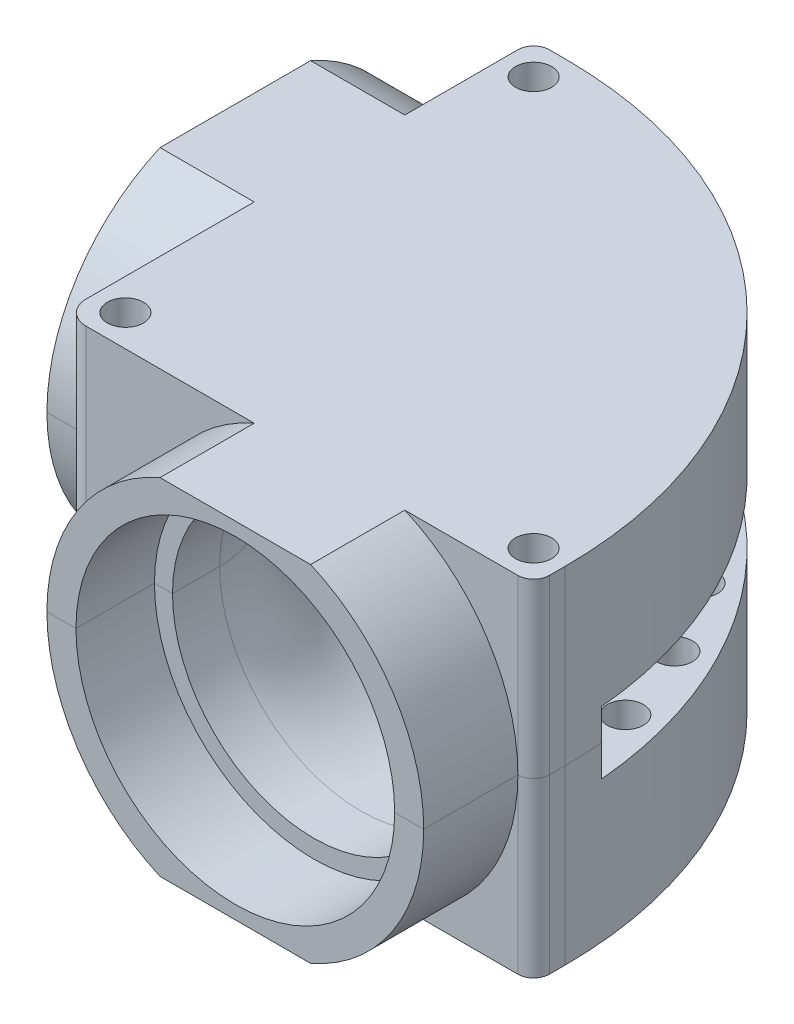
SolidWorks part; units mm, degrees
material "ABS"
ref_plane "前视基准面" through (0, 0, 0) normal (0, 0, 1) x (1, 0, 0)
ref_plane "上视基准面" through (0, 0, 0) normal (0, 1, 0) x (1, 0, 0)
ref_plane "右视基准面" through (0, 0, 0) normal (1, 0, 0) x (0, 0, -1)
sketch "草图1" plane through (0, 0, 0) normal (0, 1, 0) x (1, 0, 0)
  line L0 (2, 0) -> (28, 0)
  line L1 (0, 2) -> (0, 28)
  arc A0 (28, 0) -> (0, 28) centre (0, 0) ccw
  arc A1 (2, 0) -> (0, 2) centre (0, 0) ccw
  dimension "D1" = 56
  dimension "D2" = 4
extrude "凸台-拉伸1" add sketch "草图1" along normal mid plane 22
sketch "草图9" plane through (0, 0, 0) normal (0, 1, 0) x (1, 0, 0)
  circle A0 centre (0, 0) radius 15
  dimension "D1" = 30
sweep "切除-扫描2" cut path "草图9" circular profile diameter 18 parameters "D3"=18
sketch "草图16" plane through (0, 0, 0) normal (0, 0, 1) x (1, 0, 0)
  line L1 (2, 11) -> (28, 11)
  line L2 (2, 11) -> (2, -11)
  line L3 (2, -11) -> (28, -11)
  line L4 (28, 11) -> (28, -11)
  circle A0 centre (15, 0) radius 9
extrude "凸台-拉伸3" add sketch "草图16" along normal blind 2
sketch "草图17" plane through (0, 0, 0) normal (-1, 0, 0) x (0, 0, 1)
  line L1 (-28, 11) -> (-2, 11)
  line L2 (-28, 11) -> (-28, -11)
  line L3 (-28, -11) -> (-2, -11)
  line L4 (-2, 11) -> (-2, -11)
  circle A0 centre (-15, 0) radius 9
extrude "凸台-拉伸4" add sketch "草图17" along normal blind 2
sketch "草图18" plane through (0, 0, 2) normal (0, 0, 1) x (1, 0, 0)
  line L0 (10.2042, 11) -> (19.7958, 11)
  line L1 (28, 11) -> (2, 11) construction
  line L2 (10.2042, -11) -> (19.7958, -11)
  line L3 (2, -11) -> (28, -11) construction
  circle A0 centre (15, 0) radius 9
  arc A1 (19.7958, -11) -> (19.7958, 11) centre (15, 0) ccw
  arc A2 (10.2042, 11) -> (10.2042, -11) centre (15, 0) ccw
  dimension "D1" = 24
  dimension "D2" = 18
extrude "凸台-拉伸5" add sketch "草图18" along normal blind 6
sketch "草图19" plane through (-2, 0, 0) normal (-1, 0, 0) x (0, 0, 1)
  line L0 (-19.7958, 11) -> (-10.2042, 11)
  line L1 (-2, 11) -> (-28, 11) construction
  line L2 (-19.7958, -11) -> (-10.2042, -11)
  line L3 (-28, -11) -> (-2, -11) construction
  circle A0 centre (-15, 0) radius 9
  arc A1 (-19.7958, 11) -> (-19.7958, -11) centre (-15, 0) ccw
  arc A2 (-10.2042, -11) -> (-10.2042, 11) centre (-15, 0) ccw
  dimension "D1" = 18
  dimension "D2" = 24
extrude "凸台-拉伸6" add sketch "草图19" along normal blind 6
sketch "草图21" plane through (0, 0, 0) normal (0, 1, 0) x (1, 0, 0)
  line L0 (-2, 2) -> (-2, -2)
  line L1 (-2, -2) -> (2, -2)
  line L2 (-2, 2) -> (0, 2)
  line L3 (2, -2) -> (2, 0)
  arc A0 (0, 2) -> (2, 0) centre (0, 0) cw
extrude "凸台-拉伸8" add sketch "草图21" along normal blind 11 and the other way blind 11
sketch "草图23" plane through (0, 0, 0) normal (0, 1, 0) x (1, 0, 0)
  circle A0 centre (0, 0) radius 1.15
  dimension "D1" = 2.3
extrude "切除-拉伸1" cut sketch "草图23" against normal blind 13 and the other way blind 14
sketch "草图24" plane through (0, 0, 0) normal (0, 1, 0) x (1, 0, 0)
  line L1 (0, 0) -> (0, 40.7422) construction
  circle A0 centre (26, 0) radius 1.15
  circle A2 centre (0, 0) radius 1.15 construction
  dimension "D1" = 26
  dimension "D2" = 2.3
extrude "切除-拉伸2" cut sketch "草图24" against normal blind 11 and the other way blind 11
sketch "草图25" plane through (0, 0, 0) normal (0, 1, 0) x (1, 0, 0)
  line L0 (0, 31.2597) -> (0, -3.7756) construction
  circle A0 centre (0, 26) radius 1.15
  circle A1 centre (0, 0) radius 1.15 construction
  dimension "D1" = 2.3
  dimension "D2" = 26
extrude "切除-拉伸3" cut sketch "草图25" against normal blind 11 and the other way blind 11
sketch "草图26" plane through (0, 0, 0) normal (0, 1, 0) x (1, 0, 0)
  line L0 (0, 0) -> (0, 30.8638) construction
  line L1 (0, 0) -> (32.3971, 0) construction
  line L2 (0, 0) -> (25.3664, 25.3664) construction
  line L3 (0, 0) -> (28.117, 22.7687) construction
  line L4 (0, 0) -> (33.1084, 16.8695) construction
  line L5 (0, 0) -> (38.2313, 10.2441) construction
  line L6 (19.9239, 1.7431) -> (29.8858, 2.6147)
  line L7 (1.7431, 19.9239) -> (2.6147, 29.8858)
  arc A0 (29.8858, 2.6147) -> (2.6147, 29.8858) centre (0, 0) ccw
  arc A1 (19.9239, 1.7431) -> (1.7431, 19.9239) centre (0, 0) ccw
  circle A2 centre (0, 0) radius 26 construction
  circle A3 centre (25.1141, 6.7293) radius 1.15 construction
  dimension "D1" = 60
  dimension "D2" = 40
  dimension "D7" = 52
  dimension "D8" = 2.3
  dimension "D3" = 45
  dimension "D4" = 6
  dimension "D5" = 12
  dimension "D6" = 12
  dimension "D9" = 40
extrude "切除-拉伸6" cut sketch "草图26" against normal blind 2 and the other way blind 2
sketch "草图27" plane through (0, 0, 0) normal (0, 1, 0) x (1, 0, 0)
  line L0 (0, 0) -> (38.2313, 10.2441) construction
  line L1 (0, 0) -> (33.1084, 16.8695) construction
  line L2 (0, 0) -> (28.117, 22.7687) construction
  line L3 (0, 0) -> (25.3664, 25.3664) construction
  circle A0 centre (25.1141, 6.7293) radius 1.15
  circle A1 centre (23.1662, 11.8038) radius 1.15
  circle A2 centre (0, 0) radius 26 construction
  circle A3 centre (20.2058, 16.3623) radius 1.15
  circle A4 centre (6.7293, 25.1141) radius 1.15
  circle A5 centre (11.8038, 23.1662) radius 1.15
  circle A6 centre (16.3623, 20.2058) radius 1.15
  dimension "D1" = 2.3
  dimension "D2" = 2.3
  dimension "D3" = 2.3
extrude "切除-拉伸7" cut sketch "草图27" against normal blind 8 and the other way blind 8
sketch "草图28" plane through (0, 0, 8) normal (0, 0, 1) x (1, 0, 0)
  circle A0 centre (15, 0) radius 10.15
  dimension "D1" = 20.3
extrude "切除-拉伸8" cut sketch "草图28" against normal blind 5
sketch "草图29" plane through (-8, 0, 0) normal (-1, 0, 0) x (0, 0, 1)
  circle A0 centre (-15, 0) radius 10.15
  dimension "D1" = 20.3
fillet "圆角1" radius 1.5 1 edges at (-2, 0, 2)
fillet "圆角2" radius 1 2 edges at (-2, 0, -28) (28, 0, 2)
sketch "草图30" plane through (0, 0, 0) normal (0, 1, 0) x (1, 0, 0)
  line L1 (-10.0211, 28.814) -> (29.4552, 28.814)
  line L2 (-10.0211, 28.814) -> (-10.0211, -8.9353)
  line L3 (-10.0211, -8.9353) -> (29.4552, -8.9353)
  line L4 (29.4552, 28.814) -> (29.4552, -8.9353)
extrude "切除-拉伸10" cut sketch "草图29" against normal blind 5
split "分割1" trim tools "上视基准面" bodies to split 118 resulting bodies 120 121
